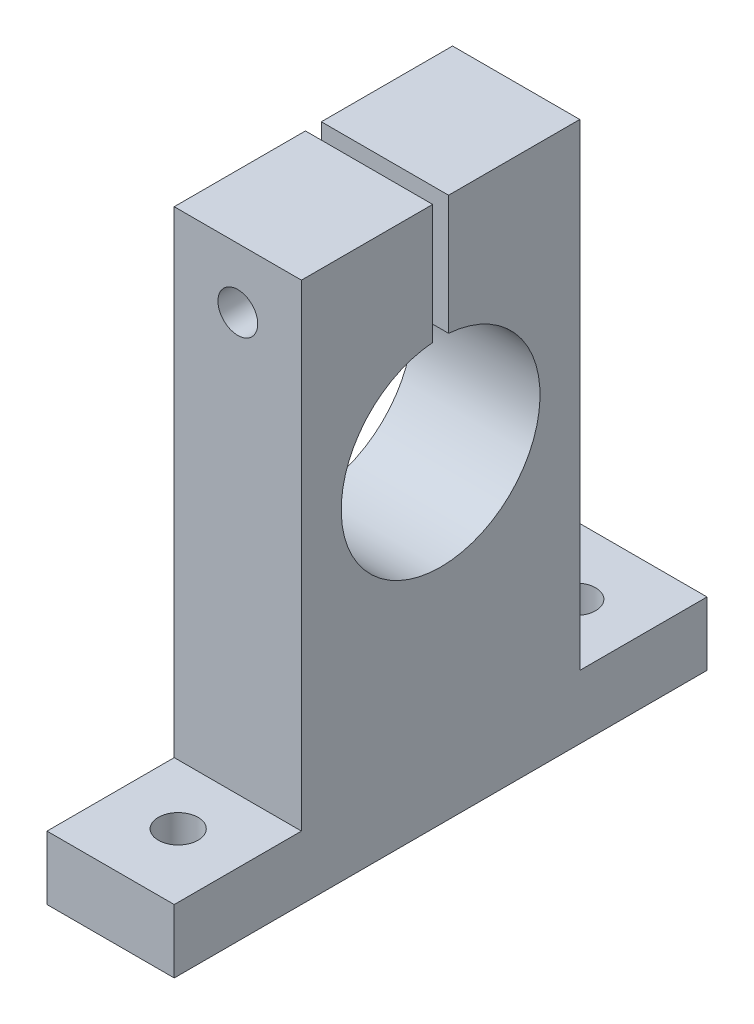
SolidWorks part; units mm, degrees
ref_plane "Top Plane" through (0, 0, 0) normal (0, 0, 1) x (1, 0, 0)
ref_plane "Right Plane" through (0, 0, 0) normal (0, 1, 0) x (1, 0, 0)
ref_plane "Front Plane" through (0, 0, 0) normal (1, 0, 0) x (0, 0, -1)
sketch "Sketch1" plane through (0, 0, 0) normal (1, 0, 0) x (0, 0, -1)
  line L0 (17.5, -32.5) -> (33.5, -32.5)
  line L1 (-17.5, 27.5) -> (-1, 27.5)
  line L2 (-17.5, 27.5) -> (-17.5, -32.5)
  line L4 (17.5, 27.5) -> (17.5, -32.5)
  line L5 (-33.5, -32.5) -> (-17.5, -32.5)
  line L6 (-33.5, -32.5) -> (-33.5, -40.5)
  line L7 (-33.5, -40.5) -> (33.5, -40.5)
  line L8 (33.5, -32.5) -> (33.5, -40.5)
  line L9 (0, 0) -> (0, -40.5) construction
  line L10 (1, 27.5) -> (17.5, 27.5)
  line L12 (-1, 27.5) -> (-1, 12.4599)
  line L13 (-1, 12.4599) -> (1, 12.4599) construction
  line L14 (1, 27.5) -> (1, 12.4599)
  line L15 (-1, 27.5) -> (1, 27.5) construction
  arc A0 (-1, 12.4599) -> (1, 12.4599) centre (0, 0) ccw
  arc A1 (1, 12.4599) -> (-1, 12.4599) centre (0, 0) ccw construction
  point P11 (-3.7732, 11.9169)
  point P13 (0, -40.5)
  dimension "D6" = 25
  dimension "D1" = 8
  dimension "D2" = 67
  dimension "D3" = 68
  dimension "D4" = 53
  dimension "D5" = 35
  dimension "D7" = 2
extrude "Boss-Extrude1" add sketch "Sketch1" along normal blind 16
sketch "Sketch2" plane through (0, -32.5, 0) normal (0, 1, 0) x (1, 0, 0)
  line L0 (8, -33.5) -> (8, -25) construction
  line L3 (16, -33.5) -> (0, -33.5) construction
  line L4 (8, -25) -> (8, 25) construction
  line L5 (8, 25) -> (8, 33.5) construction
  line L6 (16, 33.5) -> (0, 33.5) construction
  circle A0 centre (8, -25) radius 2.5
  circle A1 centre (8, 25) radius 2.5
  dimension "D1" = 5
  dimension "D2" = 50
extrude "Cut-Extrude1" cut sketch "Sketch2" against normal through all
sketch "Sketch3" plane through (0, 0, -17.5) normal (0, 0, -1) x (-1, 0, 0)
  line L0 (-16, 27.5) -> (0, 12.4599) construction
  line L1 (0, -32.5) -> (0, 27.5) construction
  circle A0 centre (-8, 19.98) radius 2.5
  point P7 (0, 0)
  point P8 (-9.2387, 21.1443)
  dimension "D1" = 5
extrude "Cut-Extrude2" cut sketch "Sketch3" against normal through all
ref_axis "Axis1" through (8, -40.5, -25) along (0, 1, 0)
ref_axis "Axis2" through (8, -40.5, 25) along (0, 1, 0)
ref_axis "Axis3" through (16, 0, 0) along (-1, 0, 0)
